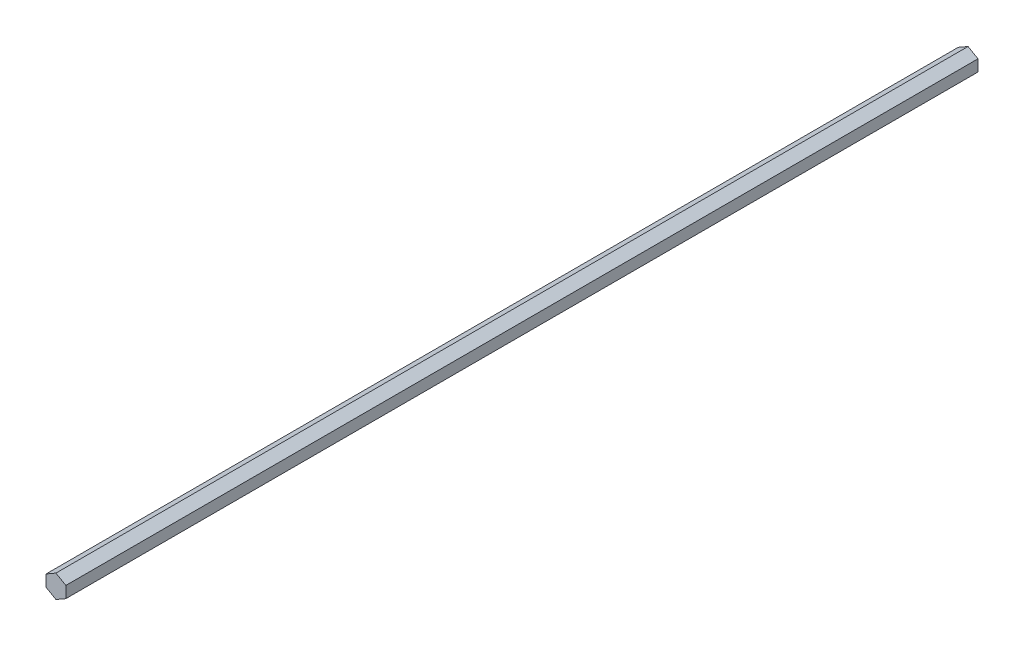
SolidWorks part; units mm, degrees
ref_plane "Front Plane" through (0, 0, 0) normal (0, 0, 1) x (1, 0, 0)
ref_plane "Top Plane" through (0, 0, 0) normal (0, 1, 0) x (1, 0, 0)
ref_plane "Right Plane" through (0, 0, 0) normal (1, 0, 0) x (0, 0, -1)
sketch "Sketch1" plane through (0, 0, 0) normal (0, 0, 1) x (1, 0, 0)
  line L1 (6.35, 3.6662) -> (0, 7.3323)
  line L2 (0, 7.3323) -> (-6.35, 3.6662)
  line L3 (-6.35, 3.6662) -> (-6.35, -3.6662)
  line L4 (-6.35, -3.6662) -> (0, -7.3323)
  line L5 (0, -7.3323) -> (6.35, -3.6662)
  line L6 (6.35, -3.6662) -> (6.35, 3.6662)
  circle A0 centre (0, 0) radius 6.35 construction
  circle A1 centre (0, 0) radius 7.3323
  dimension "D1" = 12.7
extrude "Boss-Extrude1" add sketch "Sketch1" along normal mid plane 584.2 contours L1 L2 L3 L4 L5 L6
sketch "Sketch3" plane through (0, 0, 0) normal (0, 0, 1) x (1, 0, 0)
  point P0 (0, 0)
ref_axis "Axis1" through (0, 0, 0) along (0, 0, 1)
